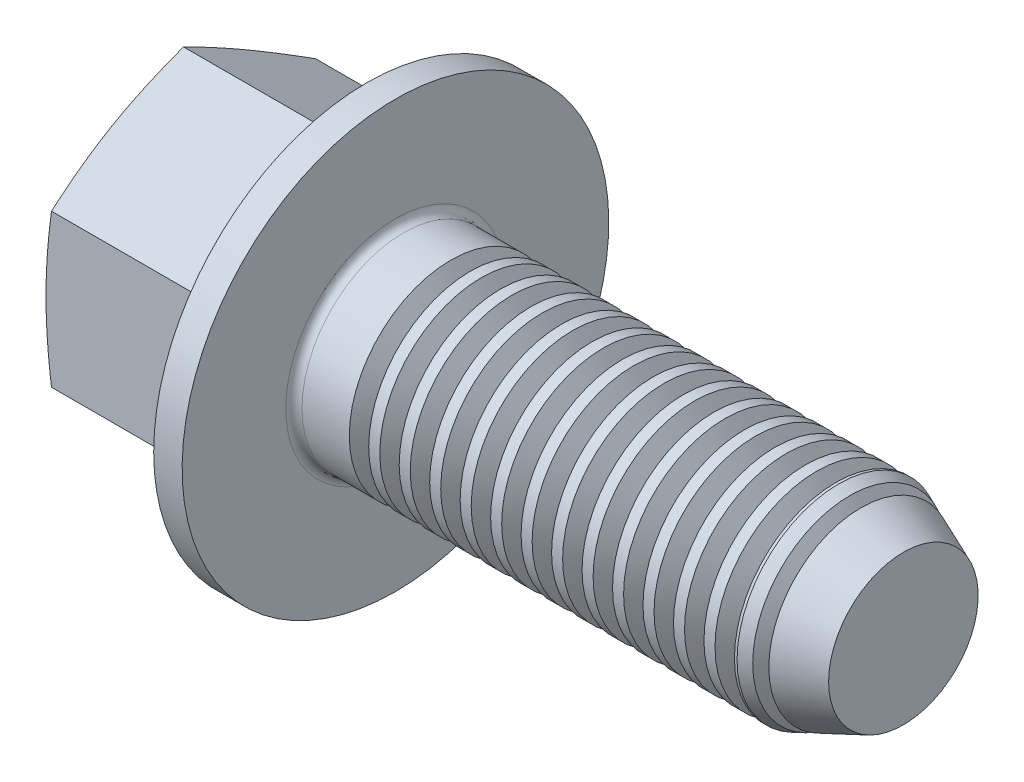
SolidWorks part; units mm, degrees
ref_plane "Front Plane" through (0, 0, 0) normal (0, 0, 1) x (1, 0, 0)
ref_plane "Top Plane" through (0, 0, 0) normal (0, 1, 0) x (1, 0, 0)
ref_plane "Right Plane" through (0, 0, 0) normal (1, 0, 0) x (0, 0, -1)
other "Configuration Table"
sketch "Sketch1" plane through (0, 0, 0) normal (0, 0, 1) x (1, 0, 0)
  line L0 (0, 0) -> (25, 0) construction
  line L1 (0, 0) -> (-10.7, 0) construction
  line L2 (0.4, 5) -> (24.172, 5)
  line L3 (25, 0) -> (25, 4.172)
  line L4 (0, 5.4) -> (0, 10.5)
  line L5 (0, 10.5) -> (-1.4, 10.5)
  line L6 (-1.4, 10.5) -> (-2.4718, 6.5)
  line L7 (-2.4718, 6.5) -> (-10.7, 6.5)
  line L8 (-10.7, 6.5) -> (-10.7, 5.2)
  line L9 (-10.7, 5.2) -> (-9.3625, 5.2)
  line L10 (-9.3625, 5.2) -> (-9.3625, 0)
  line L11 (-9.3625, 0) -> (25, 0)
  line L12 (-9.3625, 0) -> (-9.3625, 5.58) construction
  line L14 (25, 4.172) -> (24.172, 5)
  line L15 (25, 0) -> (1.5, 0) construction
  arc A0 (0.4, 5) -> (0, 5.4) centre (0.4, 5.4) cw
  dimension "D7" = 0.4
  dimension "L" = 25
  dimension "K" = 10.7
  dimension "s" = 13
  dimension "dia" = 10
  dimension "D1" = 10.4
  dimension "D2" = 1.3375
  dimension "c" = 1.4
  dimension "D4" = 15
  dimension "D5" = 45
  dimension "min" = 8.344
  dimension "B" = 23.5
  dimension "Dc" = 21
revolve "Revolve1" add sketch "Sketch1" angle 360 about L11
cosmetic thread "Cosmetic Thread1" [suppressed] parameters "D1"=22.272, "D2"=8.344
sketch "Sketch2" plane through (-10.7, 0, 0) normal (-1, 0, 0) x (0, 0, 1)
  line L1 (0, 7.5056) -> (-6.5, 3.7528)
  line L2 (-6.5, 3.7528) -> (-6.5, -3.7528)
  line L3 (-6.5, -3.7528) -> (0, -7.5056)
  line L4 (0, -7.5056) -> (6.5, -3.7528)
  line L5 (6.5, -3.7528) -> (6.5, 3.7528)
  line L6 (6.5, 3.7528) -> (0, 7.5056)
  circle A0 centre (0, 0) radius 5.2 construction
  circle A1 centre (0, 0) radius 5.2
  circle A2 centre (0, 0) radius 6.5 construction
  circle A3 centre (0, 0) radius 6.5 construction
extrude "Extrude1" add sketch "Sketch2" against normal up to next (10.7 mm away)
sketch "Sketch3" plane through (0, 0, 0) normal (0, 1, 0) x (1, 0, 0)
  line L0 (-11.5708, 3.25) -> (-9.8292, 9.75)
  line L1 (-10.7, 0) -> (-10.7, 6.5) construction
  line L2 (0, 0) -> (-3.6033, 0) construction
  line L3 (-9.8292, 9.75) -> (-11.5708, 9.75)
  line L4 (-11.5708, 9.75) -> (-11.5708, 3.25)
  dimension "D1" = 15
  dimension "D2" = 6.5
revolve "Cut-Revolve1" cut sketch "Sketch3" angle 360 about L2
fillet "Fillet1" radius 0.6 6 edges
sketch "Sketch4" plane through (0, 0, 0) normal (0, 0, 1) x (1, 0, 0)
  line L0 (0, 0) -> (5.3731, 0) construction
  line L1 (25, -4.172) -> (25, 4.172) construction
  line L3 (25, 3.68) -> (21.8132, 5)
  line L4 (0.4, 5) -> (24.172, 5) construction
  line L5 (21.8132, 5) -> (21.8132, 5.5)
  line L6 (21.8132, 5.5) -> (25, 5.5)
  line L7 (25, 5.5) -> (25, 3.68)
  dimension "D1" = 0.5
  dimension "D2" = 22.5
  dimension "Dp" = 7.36
revolve "Cut-Revolve2" cut sketch "Sketch4" angle 360 about L0
sketch "Sketch5" plane through (0, 0, 0) normal (0, 0, 1) x (1, 0, 0)
  line L0 (25, 0) -> (2.728, 0) construction
  line L1 (-9.3625, 0) -> (25, 0) construction
  line L2 (3.206, 4.172) -> (3.6841, 5)
  line L3 (3.6841, 5) -> (3.6841, 5.9561)
  line L4 (3.6841, 5.9561) -> (2.728, 5.9561)
  line L5 (2.728, 5.9561) -> (2.728, 5)
  line L6 (2.728, 5) -> (3.206, 4.172)
  dimension "B" = 22.272
  dimension "D1" = 8.344
  dimension "D2" = 10
revolve "Cut-Revolve10" cut sketch "Sketch5" angle 360 about L0
pattern_linear "LPattern10" count 15 spacing 1.5 along (1, 0, 0) of "Cut-Revolve10"
equation "\"D1@Sketch1\" = \"s@Sketch1\" / 10 * 8"
equation "\"D2@Sketch1\" = \"K@Sketch1\" / 8"
equation "\"D2@Sketch3\" = \"s@Sketch1\" / 2"
equation "\"D2@Cosmetic Thread1\" = \"min@Sketch1\""
equation "\"D1@Cosmetic Thread1\" = \"B@Sketch1\" -  ( \"dia@Sketch1\" - \"min@Sketch1\" )  / 2 - \"D7@Sketch1\""
equation "\"D1@Sketch5\" = \"D2@Cosmetic Thread1\""
equation "\"D2@Sketch5\" = \"dia@Sketch1\""
equation "\"B@Sketch5\" = \"D1@Cosmetic Thread1\""
equation "\"D1@LPattern10\" = int( \"D1@Cosmetic Thread1\" / \"D3@LPattern10\" + 0.999 ) "
